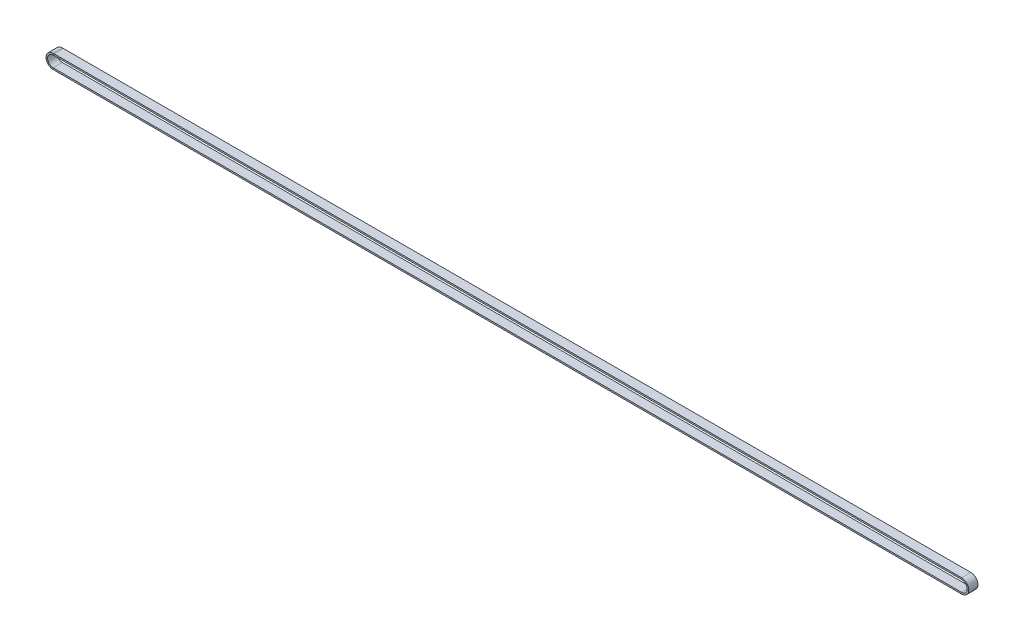
SolidWorks part; units mm, degrees
ref_plane "Front Plane" through (0, 0, 0) normal (0, 0, 1) x (1, 0, 0)
ref_plane "Top Plane" through (0, 0, 0) normal (0, 1, 0) x (1, 0, 0)
ref_plane "Right Plane" through (0, 0, 0) normal (1, 0, 0) x (0, 0, -1)
sketch "Sketch2" plane through (0, 0, -16.2334) normal (0, 0, 1) x (1, 0, 0)
  line L0 (0, 0) -> (1, 0) construction
  line L1 (0, 0) -> (0, 1) construction
  line L2 (-1, -57.8902) -> (883.5206, -57.8902)
  line L3 (883.5206, -71.6902) -> (-1, -71.6902)
  arc A0 (-1, -71.6902) -> (-1, -57.8902) centre (-1, -64.7902) cw
  arc A1 (883.5206, -57.8902) -> (883.5206, -71.6902) centre (883.5206, -64.7902) cw
sketch "Sketch3" plane through (0, 0, 0) normal (1, 0, 0) x (0, 0, -1)
  line L1 (16.2334, -59.3902) -> (7.2334, -59.3902)
  line L2 (16.2334, -59.3902) -> (16.2334, -57.8902)
  line L3 (16.2334, -57.8902) -> (7.2334, -57.8902)
  line L4 (7.2334, -59.3902) -> (7.2334, -57.8902)
  dimension "D1" = 9
  dimension "D2" = 1.5
sweep "Sweep1" add profiles "Sketch3" path "Sketch2"
